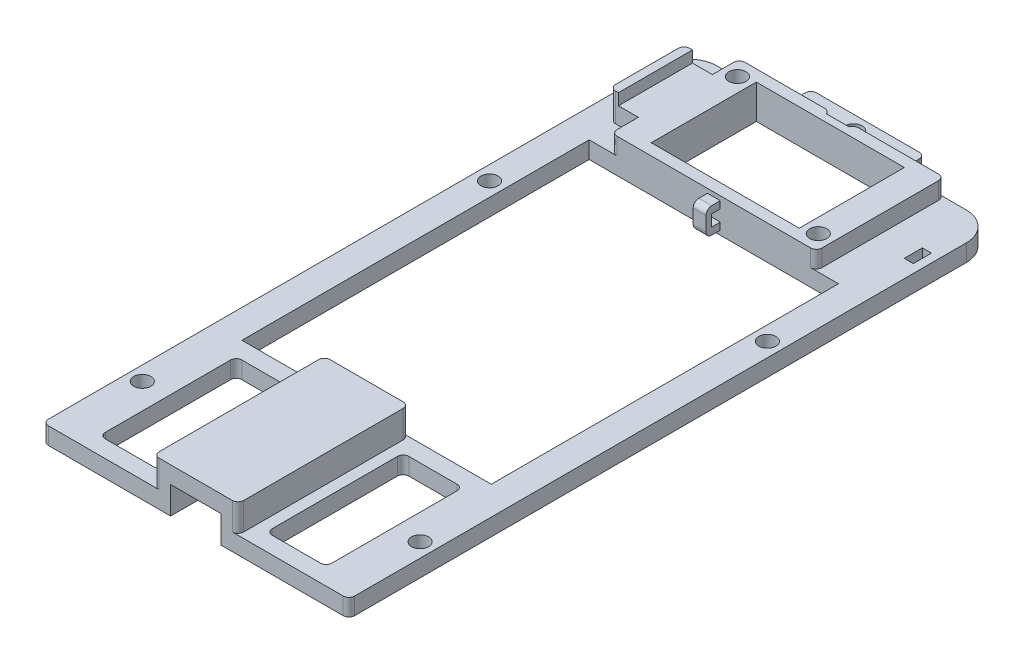
SolidWorks part; units mm, degrees
ref_plane "Front Plane" through (0, 0, 0) normal (0, 0, 1) x (1, 0, 0)
ref_plane "Top Plane" through (0, 0, 0) normal (0, 1, 0) x (1, 0, 0)
ref_plane "Right Plane" through (0, 0, 0) normal (1, 0, 0) x (0, 0, -1)
sketch "Sketch1" plane through (0, 0, 0) normal (0, 0, 1) x (1, 0, 0)
  line L0 (-26.9, 2.0451) -> (-26.9, 5.0451)
  line L1 (-26.9, 5.0451) -> (-7.42, 5.0451)
  line L2 (-7.42, 5.0451) -> (-7.42, 9.8451)
  line L3 (-7.42, 9.8451) -> (7.42, 9.8451)
  line L4 (7.42, 9.8451) -> (7.42, 5.0451)
  line L5 (7.42, 5.0451) -> (26.9, 5.0451)
  line L6 (26.9, 5.0451) -> (26.9, 2.0451)
  line L7 (26.9, 2.0451) -> (4.42, 2.0451)
  line L8 (-4.42, 2.0451) -> (-4.42, 6.8451)
  line L9 (-4.42, 6.8451) -> (4.42, 6.8451)
  line L10 (4.42, 6.8451) -> (4.42, 2.0451)
  line L11 (-4.42, 2.0451) -> (-26.9, 2.0451)
  point P2 (0, 9.8451)
  point P9 (0, 6.8451)
  dimension "D1" = 53.8
  dimension "D2" = 8.84
  dimension "D3" = 4.8
  dimension "D4" = 3
  dimension "D5" = 3
  dimension "D6" = 3
extrude "Boss-Extrude1" add sketch "Sketch1" along normal blind 30
sketch "Sketch3" plane through (0, 5.0451, 0) normal (0, 1, 0) x (1, 0, 0)
  line L0 (26.9, 0) -> (26.9, 83.4315)
  line L1 (26.9, 83.4315) -> (10, 83.47)
  line L2 (10, 83.47) -> (10, 88.1047)
  line L3 (10, 88.1047) -> (-10.0748, 88.1047)
  line L4 (-10.0748, 88.1047) -> (-10.0748, 83.47)
  line L5 (21.9, 83.47) -> (-21.9, 83.47) construction
  line L6 (-10.0748, 83.47) -> (-26.9, 83.47)
  line L7 (-26.9, 0) -> (-26.9, 83.47)
  line L8 (-26.9, 0) -> (-21.9, 0)
  line L9 (-7.42, 0) -> (-26.9, 0) construction
  line L10 (-21.9, 83.47) -> (-21.9, -52.47) construction
  line L11 (-21.9, 0) -> (-21.9, 61)
  line L12 (-21.9, 61) -> (21.9, 61)
  line L13 (21.9, -52.47) -> (21.9, 83.47) construction
  line L14 (21.9, 61) -> (21.9, 0)
  line L15 (26.9, 0) -> (7.42, 0) construction
  line L16 (21.9, 0) -> (26.9, 0)
  line L17 (-21.9, 61) -> (-25.9, 61) construction
extrude "Boss-Extrude2" add sketch "Sketch3" against normal up to surface (3 mm away) up to face at (15.66, 2.0451, 15)
sketch "Sketch4" plane through (0, 5.0451, 0) normal (0, 1, 0) x (1, 0, 0)
  line L0 (21.9, 0) -> (7.42, 0) construction
  line L1 (9.42, -3) -> (19.9, -3)
  line L2 (9.42, -3) -> (9.42, -27)
  line L3 (9.42, -27) -> (19.9, -27)
  line L4 (19.9, -3) -> (19.9, -27)
  line L5 (7.42, -30) -> (7.42, 0) construction
  line L6 (26.9, -30) -> (7.42, -30) construction
  line L7 (21.9, 61) -> (21.9, 0) construction
  line L8 (0, -4.4) -> (0, 4.4) construction
  line L9 (-19.9, -3) -> (-19.9, -27)
  line L10 (-9.42, -27) -> (-19.9, -27)
  line L11 (-9.42, -3) -> (-9.42, -27)
  line L12 (-9.42, -3) -> (-19.9, -3)
  dimension "D1" = 3
  dimension "D2" = 2
  dimension "D3" = 3
  dimension "D4" = 2
extrude "Cut-Extrude1" cut sketch "Sketch4" against normal through all
sketch "Sketch5" plane through (0, 5.0451, 0) normal (0, 1, 0) x (1, 0, 0)
  line L1 (10, 88.1047) -> (-10.0748, 88.1047) construction
  line L2 (26.9, -30) -> (26.9, 83.4315) construction
  line L3 (-26.9, -30) -> (-26.9, 83.47) construction
  line L4 (19.9, -27) -> (19.9, -3) construction
  line L5 (26.9, 32) -> (26.9, 60) construction
  circle A0 centre (24.4, -15) radius 1.5
  circle A1 centre (-24.4, -15) radius 1.5
  circle A2 centre (-0.0374, 85.6047) radius 1.5
  circle A3 centre (24.4, 46) radius 1.5
  circle A4 centre (-24.4, 46) radius 1.5
  point P13 (-0.0374, 88.1047)
  point P20 (19.9, -15)
  point P23 (26.9, 46)
  dimension "D1" = 3
  dimension "D2" = 2.5
  dimension "D3" = 2.5
  dimension "D4" = 2.5
extrude "Cut-Extrude2" cut sketch "Sketch5" against normal through all
fillet "Fillet1" radius 1 16 edges at (-9.42, 3.5451, 27) (-19.9, 3.5451, 27) (-9.42, 3.5451, 3) (-19.9, 3.5451, 3) (19.9, 3.5451, 3) (9.42, 3.5451, 3) (19.9, 3.5451, 27) (9.42, 3.5451, 27) (-10.0748, 3.5451, -88.1047) (10, 3.5451, -88.1047) (-26.9, 3.5451, 30) (-7.42, 7.4451, 0) (7.42, 7.4451, 0) (-7.42, 7.4451, 30) (7.42, 7.4451, 30) (26.9, 3.5451, 30)
sketch "Sketch7" plane through (0, 5.0451, 0) normal (0, 1, 0) x (1, 0, 0)
  line L0 (-18, 83.47) -> (-18, 78.7446)
  line L1 (26.9, -29) -> (26.9, 83.4315) construction
  line L2 (-10.0748, 83.47) -> (-26.9, 83.47) construction
  line L3 (-21.9, 61) -> (21.9, 61) construction
  line L4 (-18, 61) -> (18, 61)
  line L5 (18, 61) -> (18, 83.47)
  line L7 (18, 83.47) -> (-18, 83.47)
  line L9 (-18, 65.7446) -> (-23, 65.7446)
  line L10 (-23, 65.7446) -> (-23, 78.7446)
  line L11 (-23, 78.7446) -> (-18, 78.7446)
  line L12 (-18, 65.7446) -> (-18, 61)
  line L16 (-13, 81.47) -> (-13, 63)
  line L17 (-13, 63) -> (13, 63)
  line L18 (13, 63) -> (13, 81.47)
  line L19 (13, 81.47) -> (-13, 81.47)
  dimension "D4" = 26
  dimension "D1" = 5
  dimension "D2" = 10
  dimension "D3" = 13
  dimension "D5" = 5
  dimension "D6" = 2
  dimension "D7" = 2.7254
  dimension "D8" = 8.9
  dimension "D9" = 2
extrude "Boss-Extrude3" add sketch "Sketch7" along normal blind 3
sketch "Sketch8" plane through (0, 8.0451, 0) normal (0, 1, 0) x (1, 0, 0)
  line L0 (18, 83.47) -> (-18, 83.47) construction
  line L1 (-18, 61) -> (18, 61) construction
  line L2 (13, 63) -> (13, 81.47) construction
  line L3 (-13, 81.47) -> (-13, 63) construction
  circle A0 centre (-15.5, 80.6446) radius 1.5
  circle A1 centre (15.5, 63.8446) radius 1.5
  dimension "D5" = 3
  dimension "D1" = 2.8254
  dimension "D2" = 2.8446
  dimension "D3" = 2.5
  dimension "D4" = 2.5
extrude "Cut-Extrude3" cut sketch "Sketch8" against normal blind 4
sketch "Sketch9" plane through (0, 8.0451, 0) normal (0, 1, 0) x (1, 0, 0)
  line L0 (-23, 65.7446) -> (-18, 65.7446) construction
  line L1 (-23, 78.7446) -> (-21.5, 78.7446)
  line L2 (-23, 78.7446) -> (-23, 65.7446)
  line L3 (-23, 65.7446) -> (-21.5, 65.7446)
  line L4 (-21.5, 78.7446) -> (-21.5, 65.7446)
  dimension "D1" = 1.5
extrude "Boss-Extrude4" add sketch "Sketch9" along normal blind 2
sketch "Sketch10" plane through (0, 5.0451, 0) normal (0, 1, 0) x (1, 0, 0)
  line L1 (-13, 81.47) -> (13, 81.47)
  line L2 (-13, 81.47) -> (-13, 63)
  line L3 (-13, 63) -> (13, 63)
  line L4 (13, 81.47) -> (13, 63)
extrude "Cut-Extrude4" cut sketch "Sketch10" against normal blind 3
sketch "Sketch11" plane through (0, 8.0451, 0) normal (0, 1, 0) x (1, 0, 0)
  line L0 (-2.0374, 83.47) -> (-2.0374, 82.7919)
  line L1 (18, 83.47) -> (-18, 83.47) construction
  line L3 (-2.0374, 82.7919) -> (1.9626, 82.7919)
  line L4 (1.9626, 82.7919) -> (1.9626, 83.47)
  line L5 (1.9626, 83.47) -> (-2.0374, 83.47)
  circle A0 centre (-0.0374, 85.6047) radius 1.5 construction
  dimension "D1" = 2
  dimension "D2" = 2
extrude "Cut-Extrude5" cut sketch "Sketch11" against normal up to surface (3 mm away) up to face at (-0.0374, 5.0451, -84.1047)
fillet "Fillet2" radius 1 8 edges at (-23, 7.5451, -65.7446) (-23, 7.5451, -78.7446) (-18, 6.5451, -83.47) (-18, 6.5451, -61) (1.9626, 6.5451, -83.47) (-2.0374, 6.5451, -83.47) (18, 6.5451, -61) (18, 6.5451, -83.47)
fillet "Fillet3" radius 5 2 edges at (26.9, 3.5451, -83.4315) (-26.9, 3.5451, -83.47)
sketch "Sketch12" plane through (0, 5.0451, 0) normal (0, 1, 0) x (1, 0, 0)
  line L0 (18, 72.235) -> (26.9, 72.235) construction
  line L1 (18, 62) -> (18, 82.47) construction
  line L2 (26.9, -29) -> (26.9, 78.4429) construction
  line L3 (-26.9, -29) -> (-26.9, 78.47) construction
  line L4 (23.8, 73.835) -> (25.4, 73.835)
  line L5 (23.8, 73.835) -> (23.8, 70.635)
  line L6 (23.8, 70.635) -> (25.4, 70.635)
  line L7 (25.4, 73.835) -> (25.4, 70.635)
  line L8 (23.8, 73.835) -> (25.4, 70.635) construction
  line L9 (23.8, 70.635) -> (25.4, 73.835) construction
  line L10 (-25.65, 74.635) -> (-24.05, 74.635)
  line L11 (-25.65, 74.635) -> (-25.65, 69.835)
  line L12 (-25.65, 69.835) -> (-24.05, 69.835)
  line L13 (-24.05, 74.635) -> (-24.05, 69.835)
  line L14 (-25.65, 74.635) -> (-24.05, 69.835) construction
  line L15 (-25.65, 69.835) -> (-24.05, 74.635) construction
  point P6 (24.6, 72.235)
  point P11 (-24.85, 72.235)
  dimension "D1" = 1.6
  dimension "D2" = 3.2
  dimension "D3" = 1.5
  dimension "D4" = 1.6
  dimension "D5" = 4.8
  dimension "1.25" = 1.25
extrude "Cut-Extrude6" cut sketch "Sketch12" against normal up to surface (3 mm away) up to face at (0, 2.0451, -72.235)
sketch "Sketch13" plane through (0, 0, -61) normal (0, 0, 1) x (1, 0, 0)
  line L0 (-1.125, 7.2951) -> (1.125, 7.2951)
  line L1 (-1.125, 6.0451) -> (1.125, 6.0451)
  line L2 (-1.125, 7.2951) -> (-1.125, 6.0451)
  line L3 (1.125, 7.2951) -> (1.125, 6.0451)
  line L4 (1.125, 4.0451) -> (1.125, 2.7951)
  line L5 (1.125, 2.7951) -> (-1.125, 2.7951)
  line L6 (-1.125, 2.7951) -> (-1.125, 4.0451)
  line L7 (-1.125, 4.0451) -> (1.125, 4.0451)
  line L8 (-17, 8.0451) -> (17, 8.0451) construction
  point P3 (0, 7.2951)
  point P6 (0, 6.0451)
  dimension "D1" = 1.25
  dimension "D2" = 2.25
  dimension "D3" = 1.25
  dimension "D4" = 2
  dimension "D5" = 0.75
extrude "Boss-Extrude5" add sketch "Sketch13" along normal blind 1.5
sketch "Sketch14" plane through (0, 0, -59.5) normal (0, 0, 1) x (1, 0, 0)
  line L1 (-1.125, 2.7951) -> (1.125, 2.7951)
  line L2 (-1.125, 2.7951) -> (-1.125, 7.2951)
  line L3 (-1.125, 7.2951) -> (1.125, 7.2951)
  line L4 (1.125, 2.7951) -> (1.125, 7.2951)
extrude "Boss-Extrude6" add sketch "Sketch14" along normal blind 1
fillet "Fillet4" radius 1 2 edges at (0, 2.7951, -58.5) (0, 7.2951, -58.5)
